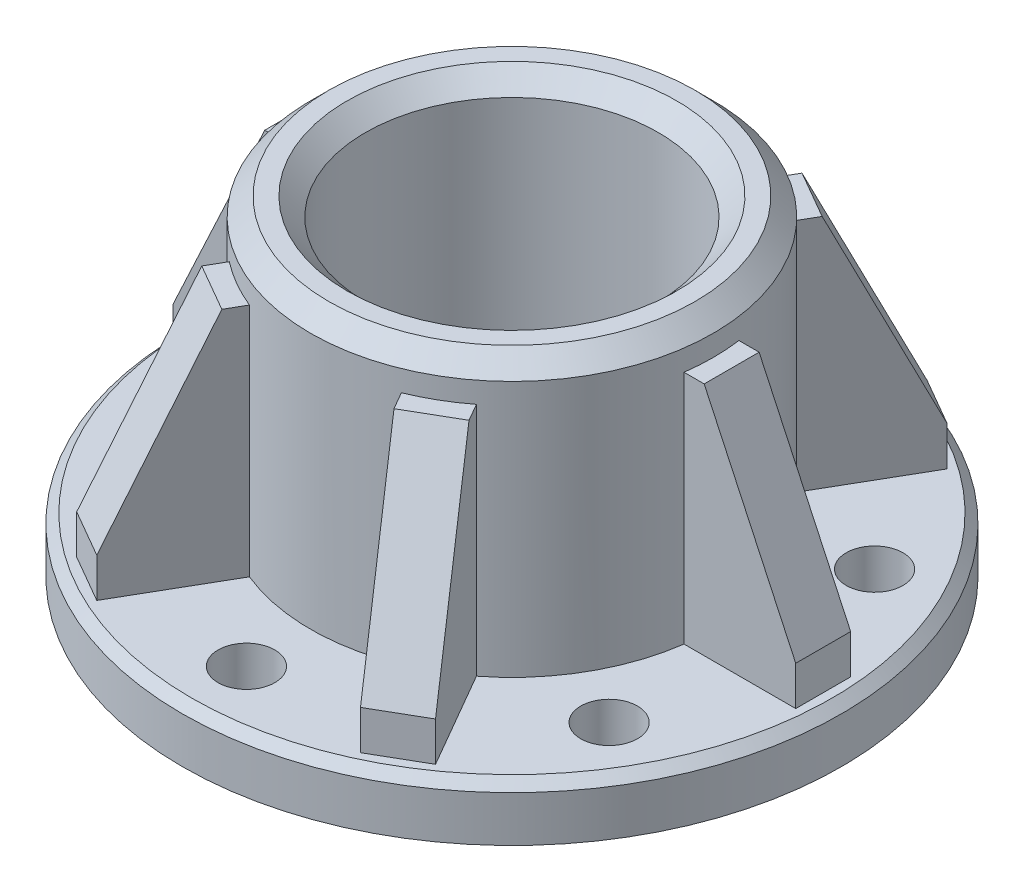
SolidWorks part; units mm, degrees
ref_plane "Front Plane" through (0, 0, 0) normal (0, 0, 1) x (1, 0, 0)
ref_plane "Top Plane" through (0, 0, 0) normal (0, 1, 0) x (1, 0, 0)
ref_plane "Right Plane" through (0, 0, 0) normal (1, 0, 0) x (0, 0, -1)
sketch "Sketch1" plane through (0, 0, 0) normal (0, 1, 0) x (1, 0, 0)
  circle A0 centre (0, 0) radius 8
  circle A1 centre (0, 0) radius 18
  dimension "D1" = 16
  dimension "D2" = 10
extrude "Boss-Extrude1" add sketch "Sketch1" along normal blind 3
sketch "Sketch2" plane through (0, 3, 0) normal (0, 1, 0) x (1, 0, 0)
  circle A0 centre (0, 0) radius 11
  circle A1 centre (0, 0) radius 8 construction
  circle A2 centre (0, 0) radius 8
  dimension "D1" = 3
extrude "Boss-Extrude2" add sketch "Sketch2" along normal blind 15
sketch "Sketch3" plane through (0, 3, 0) normal (0, 1, 0) x (1, 0, 0)
  line L0 (0, 0) -> (18, 0) construction
  line L1 (0, 0) -> (15.5885, -9) construction
  line L2 (9.5263, -5.5) -> (15.5885, -9) construction
  circle A0 centre (0, 0) radius 18 construction
  circle A1 centre (0, 0) radius 11 construction
  circle A2 centre (0, 0) radius 11
  point P10 (12.5574, -7.25)
  point P14 (0, -14.5)
  point P15 (-12.5574, -7.25)
  point P16 (-12.5574, 7.25)
  point P17 (0, 14.5)
  point P18 (12.5574, 7.25)
  point P19 (0, 0)
  dimension "D1" = 30
  dimension "D2" = 6
ref_point "Point1"
ref_point "Point2"
ref_point "Point3"
hole_wizard "M (0.295) Diameter Hole1" positions "3DSketch1" profile "Sketch4" hole size "M" standard "ANSI Inch" end condition through all
sketch3d "3DSketch1"
  point P0 (0, 3, 14.5)
  point P3 (-12.5574, 3, 7.25)
  point P6 (12.5574, 3, 7.25)
  point P9 (12.5574, 3, -7.25)
  point P12 (0, 3, -14.5)
  point P15 (-12.5574, 3, -7.25)
sketch "Sketch4" plane through (0, 3, 14.5) normal (1, 0, 0) x (0, 0, 1)
  line L0 (0, 0) -> (0, 3)
  line L1 (0, 3) -> (1.55, 3)
  line L2 (1.55, 3) -> (1.55, 0)
  line L5 (1.55, 0) -> (0, 0)
  line L11 (0, -6.35) -> (0, 107.95) construction
  dimension "Thru Hole Dia." = 3.1
  dimension "Thru Hole Depth" = 3
ref_plane "Plane1" through (0, 0, 0) normal (0, 0, 1) x (1, 0, 0)
sketch "Sketch5" plane through (0, 0, 0) normal (0, 0, 1) x (1, 0, 0)
  line L0 (11, 18) -> (18, 3) construction
  line L1 (12, 15.8571) -> (17, 5.1429)
  line L2 (12, 15.8571) -> (11, 15.8571)
  line L4 (11, 3) -> (11, 18) construction
  line L6 (11, 15.8571) -> (10.9, 15.8571)
  line L7 (17, 5.1429) -> (17, 3)
  line L8 (0, 3) -> (18, 3) construction
  line L9 (17, 3) -> (17, 2.9)
  line L10 (17, 2.9) -> (10.9, 3)
  line L11 (10.9, 3) -> (10.9, 15.8571)
  dimension "D1" = 1
  dimension "D2" = 1
  dimension "D3" = 0.1
  dimension "D4" = 0.1
extrude "Boss-Extrude3" add sketch "Sketch5" along normal mid plane 3
ref_axis "Axis1" through (0, 18, 0) along (0, -1, 0)
pattern_circular "CirPattern1" count 6 over 360 about axis through (0, 18, 0) along (0, -1, 0) of "Boss-Extrude3"
chamfer "Chamfer1" distance 1 angle 45 2 edges at (0, 18, 8) (0, 18, 11)
chamfer "Chamfer2" distance 0.5 angle 45 1 edges at (0, 3, 18)
